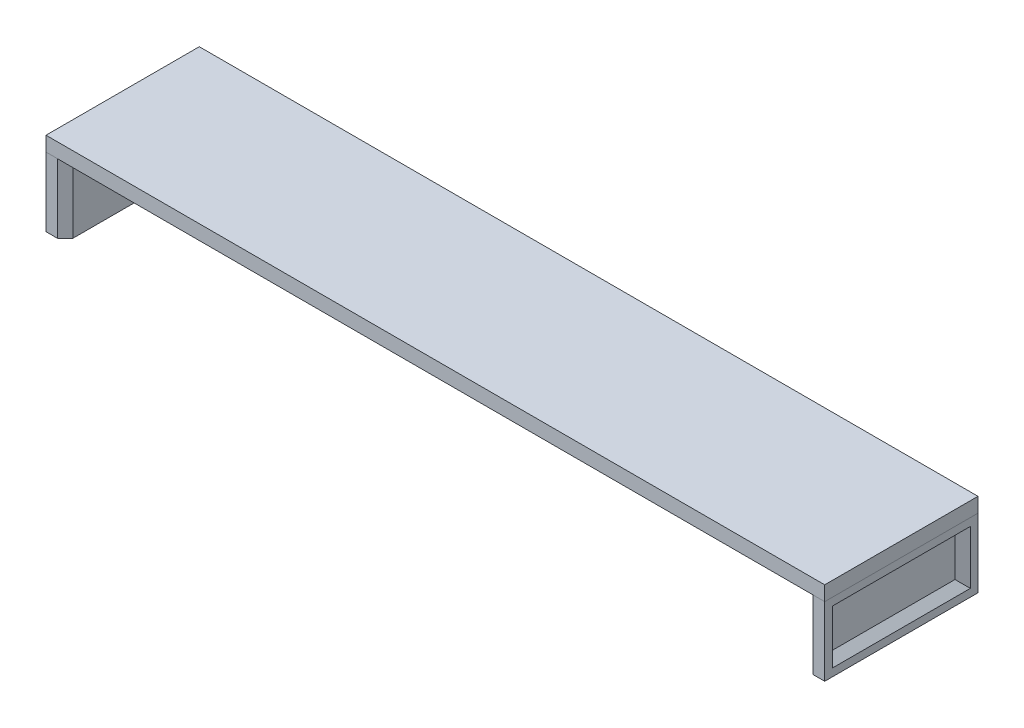
SolidWorks part; units mm, degrees
ref_plane "Front Plane" through (0, 0, 0) normal (0, 0, 1) x (1, 0, 0)
ref_plane "Top Plane" through (0, 0, 0) normal (0, 1, 0) x (1, 0, 0)
ref_plane "Right Plane" through (0, 0, 0) normal (1, 0, 0) x (0, 0, -1)
sketch "Sketch1" plane through (0, 0, 0) normal (0, 1, 0) x (1, 0, 0)
  line L1 (0, 0) -> (1016, 0)
  line L2 (0, 0) -> (0, 200)
  line L3 (0, 200) -> (1016, 200)
  line L4 (1016, 0) -> (1016, 200)
  dimension "D1" = 1016
  dimension "D2" = 200
extrude "Boss-Extrude1" add sketch "Sketch1" along normal blind 19.05
sketch "Sketch2" plane through (0, 0, 0) normal (0, -1, 0) x (1, 0, 0)
  line L0 (0, 0) -> (1016, 0) construction
  line L1 (0, -200) -> (25, -200)
  line L2 (0, -200) -> (0, 0)
  line L3 (0, 0) -> (25, 0)
  line L4 (25, -200) -> (25, 0)
  dimension "D1" = 25
extrude "Boss-Extrude3" add sketch "Sketch2" along normal blind 90 separate body
ref_plane "Plane1" through (508, 0, 0) normal (-1, 0, 0) x (0, 0, 1)
sketch "Sketch8" plane through (0, 0, 0) normal (-1, 0, 0) x (0, 0, 1)
  line L8 (-10, -10) -> (-190, -10)
  line L9 (-190, -10) -> (-190, -80)
  line L10 (-190, -80) -> (-10, -80)
  line L11 (-10, -80) -> (-10, -10)
  line L12 (-10, -10) -> (-190, -10)
  line L13 (-190, -10) -> (-190, -80)
  line L14 (-190, -80) -> (-10, -80)
  line L15 (-10, -80) -> (-10, -10)
  dimension "D1" = 10
extrude "Cut-Extrude5" cut sketch "Sketch8" against normal blind 10
chamfer "Chamfer2" distance 10 angle 45 4 edges at (10, -80, -100) (10, -45, -190) (10, -10, -100) (10, -45, -10)
sketch "Sketch10" plane through (0, 0, 0) normal (0, -1, 0) x (1, 0, 0)
  line L0 (0, 0) -> (25, 0)
  line L1 (25, -200) -> (25, -175)
  line L2 (1016, -200) -> (0, -200) construction
  line L3 (25, 0) -> (25, -25)
  line L4 (25, -25) -> (32.5, -25)
  line L5 (25, -200) -> (25, 0) construction
  line L6 (25, -175) -> (32.5, -175)
  line L7 (25, -100) -> (31.4266, -100)
  line L8 (25, -187.8531) -> (25, -162.1469)
  line L9 (25, -37.8531) -> (25, -12.1469)
  circle A1 centre (32.5, -175) radius 3
  circle A3 centre (32.5, -25) radius 3
  circle A4 centre (32.5, -25) radius 7.5
  circle A6 centre (32.5, -175) radius 7.5
  arc A7 (32.5, -167.5) -> (25, -162.1469) centre (31.4266, -161.0734) cw
  arc A8 (32.5, -182.5) -> (25, -187.8531) centre (31.4266, -188.9266) ccw
  arc A9 (32.5, -17.5) -> (25, -12.1469) centre (31.4266, -11.0734) cw
  arc A10 (32.5, -32.5) -> (25, -37.8531) centre (31.4266, -38.9266) ccw
  point P6 (0, 0)
  point P33 (0, 0)
  dimension "D2" = 15
  dimension "D3" = 6
  dimension "D4" = 15
  dimension "D1" = 25
  dimension "D5" = 25
extrude "Boss-Extrude6" add sketch "Sketch10" along normal blind 10 separate body contours A10 A4 A9 A3 | A10 A4 L9 | A4 A9 L3 | A8 A6 A7 A1 | A8 A6 L1 | A6 A7 L8 region at (26.5286, 0, -182.0414) region at (26.5286, 0, -167.9586) region at (26.9659, 0, -170.258) region at (26.5286, 0, -17.9586) region at (26.5286, 0, -32.0414) region at (26.9659, 0, -20.258)
combine bodies "Combine2" operation type add bodies to combine 108 115 116
chamfer "Chamfer4" distance 2.5 angle 45 2 edges at (32.5, -10, -178) (32.5, -10, -28)
chamfer "Chamfer5" distance 10 angle 45 2 edges at (25, -45, 0) (25, -45, -200)
mirror "Mirror1" about plane through (508, 0, 0) normal (-1, 0, 0) of bodies 117
